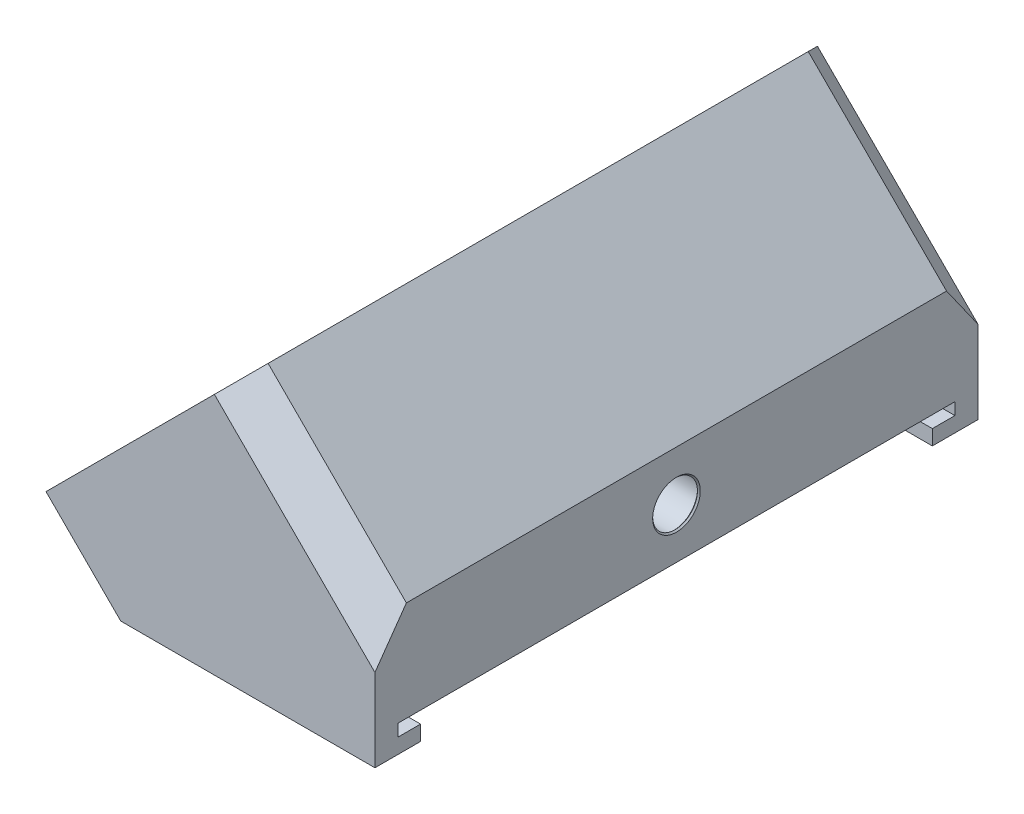
SolidWorks part; units mm, degrees
ref_plane "Front Plane" through (0, 0, 0) normal (0, 0, 1) x (1, 0, 0)
ref_plane "Top Plane" through (0, 0, 0) normal (0, 1, 0) x (1, 0, 0)
ref_plane "Right Plane" through (0, 0, 0) normal (1, 0, 0) x (0, 0, -1)
sketch "Sketch1" plane through (0, 0, 0) normal (0, 0, 1) x (1, 0, 0)
  line L1 (431.7344, 53.7575) -> (431.7344, 87.5274)
  line L2 (352.3672, 53.7575) -> (431.7344, 53.7575)
  line L3 (431.7344, 56.7575) -> (431.7344, 87.5274) construction
  line L4 (349.3672, 56.7575) -> (338.4153, 67.7095) construction
  line L5 (350.4348, 59.9325) -> (350.4348, 63.1075)
  line L6 (348.1245, 53.7575) -> (434.7344, 53.7575) construction
  line L40 (344.8775, 74.1717) -> (346.9988, 72.0504) construction
  line L44 (392.5627, 121.8569) -> (338.4153, 67.7095)
  line L45 (431.7344, 87.5274) -> (394.9838, 124.278)
  line L46 (352.3672, 53.7575) -> (338.4153, 67.7095)
  line L47 (350.4348, 59.9325) -> (431.7344, 59.9325)
  line L48 (350.4348, 63.1075) -> (431.7344, 63.1075)
  line L83 (390.7412, 115.7927) -> (388.6198, 117.914)
  line L84 (392.5627, 121.8569) -> (394.9838, 124.278)
  line L87 (350.4348, 59.9325) -> (342.6579, 67.7095)
  line L90 (390.7412, 115.7927) -> (394.9838, 120.0354)
  line L91 (431.7344, 83.2848) -> (394.9838, 120.0354)
  line L92 (346.9988, 72.0504) -> (342.6579, 67.7095)
  line L95 (348.1245, 53.7575) -> (334.1726, 67.7095) construction
  line L96 (390.4414, 123.9782) -> (334.1726, 67.7095) construction
  line L97 (434.7344, 88.7701) -> (394.9838, 128.5206) construction
  line L98 (390.4414, 123.9782) -> (394.9838, 128.5206) construction
  line L99 (434.7344, 53.7575) -> (434.7344, 88.7701) construction
  line L100 (349.3672, 56.7575) -> (431.7344, 56.7575) construction
  dimension "D1" = 3
extrude "Boss-Extrude1" add sketch "Sketch1" along normal blind 160.26 contours L44 L40 L92 L87 L47 L48 L91 L90 L83 | L91 L48 L45 L84 L44 L83 L90 | L48 L47 | L40 L44 L46 L47 L87 L92 region at (390.1689, 79.8182, 0) region at (391.0846, 61.52, 0) region at (410.703, 105.7776, 0)
sketch "Sketch2" plane through (135.3529, -135.3529, 0) normal (-0.7071, 0.7071, 0) x (0, 0, 1)
  line L0 (0, 367.1735) -> (160.26, 367.1735)
  line L1 (160.26, 367.1735) -> (0, 367.1735) construction
  line L2 (160.26, 367.1735) -> (160.26, 287.1735)
  line L3 (160.26, 287.1735) -> (0, 287.1735)
  line L4 (0, 287.1735) -> (0, 367.1735)
  line L5 (148.13, 364.1735) -> (148.13, 290.1735)
  line L6 (12.13, 364.1735) -> (148.13, 364.1735)
  line L11 (148.13, 290.1735) -> (12.13, 290.1735)
  line L13 (3, 290.1735) -> (3, 364.1735) construction
  line L14 (157.26, 364.1735) -> (157.26, 290.1735) construction
  line L15 (12.13, 290.1735) -> (12.13, 364.1735)
  line L16 (3, 364.1735) -> (157.26, 364.1735) construction
  line L17 (157.26, 290.1735) -> (3, 290.1735) construction
  dimension "D2" = 3
extrude "Cut-Extrude1" cut sketch "Sketch2" against normal blind 156 flip side to cut
sketch "Sketch11" plane through (135.3529, -135.3529, 0) normal (-0.7071, 0.7071, 0) x (0, 0, 1)
  line L0 (7.63, 353.5885) -> (7.63, 327.1735) construction
  line L1 (7.63, 300.7585) -> (152.63, 300.7585) construction
  line L2 (152.63, 300.7585) -> (152.63, 353.5885) construction
  line L3 (152.63, 353.5885) -> (7.63, 353.5885) construction
  line L4 (0, 327.1735) -> (160.26, 327.1735) construction
  line L7 (0, 367.1735) -> (0, 287.1735) construction
  line L8 (160.26, 367.1735) -> (160.26, 287.1735) construction
  line L9 (7.63, 327.1735) -> (7.63, 300.7585) construction
  line L10 (80.13, 367.1735) -> (80.13, 287.1735) construction
  line L11 (160.26, 367.1735) -> (0, 367.1735) construction
  line L12 (160.26, 287.1735) -> (0, 287.1735) construction
  circle A0 centre (7.63, 353.5885) radius 1.778
  circle A1 centre (7.63, 300.7585) radius 1.778
  circle A2 centre (152.63, 353.5885) radius 1.778
  circle A4 centre (152.63, 300.7585) radius 1.778
  dimension "D1" = 145
  dimension "D2" = 72.5
extrude "Cut-Extrude8" cut sketch "Sketch11" against normal blind 6
sketch "Sketch17" plane through (0, 0, 12.13) normal (0, 0, 1) x (1, 0, 0)
  line L0 (431.7344, 83.2848) -> (431.7344, 53.7575)
  line L20 (428.7344, 86.2848) -> (428.7344, 53.7575)
  line L21 (431.7344, 53.7575) -> (428.7344, 53.7575)
  line L22 (431.7344, 83.2848) -> (428.7344, 86.2848)
  line L24 (428.7344, 83.2848) -> (428.7344, 53.7575) construction
  dimension "D1" = 3
extrude "Boss-Extrude14" add sketch "Sketch17" along normal up to next
sketch "Sketch19" plane through (431.7344, 0, 0) normal (1, 0, 0) x (0, 0, -1)
  line L0 (-160.26, 53.7575) -> (0, 53.7575)
  line L1 (-154.13, 57.7575) -> (-6.13, 57.7575)
  line L6 (-154.13, 60.9575) -> (-6.13, 60.9575)
  line L8 (-80.13, 87.5274) -> (-80.13, 49.2515) construction
  line L10 (-160.26, 87.5274) -> (0, 87.5274) construction
  line L11 (-6.13, 87.5274) -> (-6.13, 49.2515) construction
  line L12 (-154.13, 60.9575) -> (-154.13, 57.7575)
  line L17 (-6.13, 60.9575) -> (-6.13, 57.7575)
  line L20 (-154.13, 87.5274) -> (-154.13, 49.2515) construction
  point P4 (-156, 59.7575)
  point P5 (-4, 57.7575)
  point P6 (-156, 62.9575)
  point P7 (-4, 60.9575)
  dimension "D4" = 74
  dimension "D6" = 74
extrude "Cut-Extrude13" cut sketch "Sketch19" against normal blind 79.12 contours L6 L17 L1 region at (431.7344, 59.3575, 80.13)
sketch "Sketch24" plane through (431.7344, 0, 0) normal (1, 0, 0) x (0, 0, -1)
  line L0 (-12.13, 57.7575) -> (-12.13, 53.7575)
  line L2 (-148.13, 53.7575) -> (-12.13, 53.7575)
  line L4 (-12.13, 57.7575) -> (-148.13, 57.7575)
  line L5 (-148.13, 57.7575) -> (-148.13, 53.7575)
extrude "Cut-Extrude15" cut sketch "Sketch24" against normal blind 3
sketch "Sketch29" plane through (0, 0, 12.13) normal (0, 0, 1) x (1, 0, 0)
  line L0 (356.6098, 53.7575) -> (372.6098, 53.7575)
  line L1 (431.7344, 53.7575) -> (356.6098, 53.7575) construction
  line L2 (372.6098, 53.7575) -> (372.6098, 57.7575)
  line L3 (431.7344, 57.7575) -> (352.6144, 57.7575) construction
  line L4 (372.6098, 57.7575) -> (352.6098, 57.7575)
  line L5 (356.6098, 53.7575) -> (340.5366, 69.8308) construction
  line L6 (352.6098, 57.7575) -> (356.6098, 53.7575)
extrude "Boss-Extrude16" add sketch "Sketch29" along normal up to next
chamfer "Chamfer2" distance 8.36 angle 45 4 edges at (413.3591, 105.9027, 160.26) (345.3912, 60.7335, 160.26) (345.3912, 60.7335, 0) (413.3591, 105.9027, 0)
sketch "Sketch31" plane through (0, 53.7575, 0) normal (0, -1, 0) x (1, 0, 0)
  line L0 (352.3672, 80.13) -> (430.6676, 80.13) construction
  line L1 (352.3672, 151.9) -> (352.3672, 8.36) construction
  line L2 (372.6098, 12.13) -> (372.6098, 6.13)
  line L3 (397.6098, 154.13) -> (397.6098, 148.13)
  line L4 (372.6098, 6.13) -> (397.6098, 6.13)
  line L5 (372.6098, 148.13) -> (397.6098, 148.13)
  line L7 (372.6098, 154.13) -> (397.6098, 154.13) construction
  line L8 (372.6098, 148.13) -> (431.7344, 148.13) construction
  line L10 (372.6098, 12.13) -> (372.6098, 6.13)
  line L12 (372.6098, 6.13) -> (397.6098, 6.13)
  line L18 (372.6098, 154.13) -> (397.6098, 154.13)
  line L19 (372.6098, 148.13) -> (372.6098, 154.13)
  line L20 (372.6098, 12.13) -> (397.6098, 12.13)
  line L21 (397.6098, 6.13) -> (397.6098, 12.13)
  line L22 (372.6098, 12.13) -> (397.6098, 12.13)
  line L23 (397.6098, 6.13) -> (397.6098, 12.13)
  line M11 (431.7344, 12.13) -> (372.6098, 12.13)
  line M13 (372.6098, 148.13) -> (431.7344, 148.13)
  dimension "D2" = 25
  dimension "D4" = 6
extrude "Cut-Extrude19" cut sketch "Sketch31" against normal up to next contours L19 L3 L18 M13 | L4 L21 L2 M11 region at (385.1098, 53.7575, 9.13) region at (385.1098, 53.7575, 151.13)
sketch "Sketch32" plane through (431.7344, 0, 0) normal (1, 0, 0) x (0, 0, -1)
  line L0 (-80.13, 87.5274) -> (-80.13, 60.9575) construction
  line L1 (-151.9, 87.5274) -> (-8.36, 87.5274) construction
  line L2 (-154.13, 60.9575) -> (-6.13, 60.9575) construction
  circle A0 centre (-80.13, 74.2425) radius 6.7
  dimension "D1" = 13.4
extrude "Cut-Extrude20" cut sketch "Sketch32" against normal blind 10
sketch "Sketch33" plane through (428.7344, 0, 0) normal (-1, 0, 0) x (0, 0, 1)
  circle A0 centre (80.13, 74.2425) radius 6.7
  circle A1 centre (80.13, 74.2425) radius 9.2
  dimension "D2" = 13.4
  dimension "D1" = 2.5
extrude "Boss-Extrude17" add sketch "Sketch33" along normal blind 10
sketch "Sketch34" plane through (418.7344, 0, 0) normal (-1, 0, 0) x (0, 0, 1)
  circle A0 centre (80.13, 74.2425) radius 9
  circle A1 centre (80.13, 74.2425) radius 5.5
  dimension "D1" = 3.5
extrude "Boss-Extrude18" add sketch "Sketch34" against normal blind 2
sketch "Sketch35" plane through (431.7344, 0, 0) normal (1, 0, 0) x (0, 0, -1)
  circle A0 centre (-80.13, 74.2425) radius 6.7
  circle A1 centre (-80.13, 74.2425) radius 5.95
  dimension "D2" = 13.4
  dimension "D1" = 0.75
extrude "Boss-Extrude19" add sketch "Sketch35" against normal blind 0.75
chamfer "Chamfer4" distance 0.375 angle 45 2 edges at (430.9844, 74.2425, 74.18) (431.7344, 74.2425, 74.18)
sketch "Sketch36" plane through (428.7344, 0, 0) normal (-1, 0, 0) x (0, 0, 1)
  line L0 (12.13, 86.2848) -> (12.13, 60.9575)
  line L1 (12.13, 60.9575) -> (148.13, 60.9575)
  line L2 (148.13, 60.9575) -> (148.13, 86.2848)
  line L3 (148.13, 86.2848) -> (12.13, 86.2848)
  circle A0 centre (80.13, 74.2425) radius 9.2
extrude "Boss-Extrude20" add sketch "Sketch36" along normal up to surface (10 mm away) up to face at (418.7344, 74.2425, 89.33)
sketch "Sketch37" plane through (0, 0, 148.13) normal (0, 0, -1) x (-1, 0, 0)
  line L0 (-418.7344, 86.2848) -> (-418.7344, 96.2848)
  line L1 (-428.7344, 86.2848) -> (-392.8625, 122.1567) construction
  line L2 (-418.7344, 96.2848) -> (-428.7344, 86.2848)
  line L3 (-428.7344, 86.2848) -> (-418.7344, 86.2848)
extrude "Boss-Extrude21" add sketch "Sketch37" along normal up to surface (136 mm away) up to face at (414.6721, 55.7575, 12.13)
sketch "Sketch38" plane through (0, 60.9575, 0) normal (0, -1, 0) x (1, 0, 0)
  line L0 (418.7344, 80.13) -> (431.7344, 80.13) construction
  line L1 (418.7344, 12.13) -> (418.7344, 148.13) construction
  line L2 (431.7344, 154.13) -> (431.7344, 6.13) construction
  line L3 (418.7344, 40.13) -> (431.7344, 40.13) construction
  line L4 (418.7344, 120.13) -> (431.7344, 120.13) construction
  circle A0 centre (425.2344, 120.13) radius 2.55
  circle A1 centre (425.2344, 40.13) radius 2.55
  dimension "D3" = 5.1
  dimension "D1" = 40
  dimension "D2" = 40
extrude "Cut-Extrude23" cut sketch "Sketch38" against normal blind 3.8
sketch "Sketch39" plane through (0, 64.7575, 0) normal (0, -1, 0) x (1, 0, 0)
  circle A0 centre (425.2344, 120.13) radius 1.8
  circle A1 centre (425.2344, 40.13) radius 1.8
  dimension "D1" = 3.6
extrude "Cut-Extrude24" cut sketch "Sketch39" against normal blind 5
